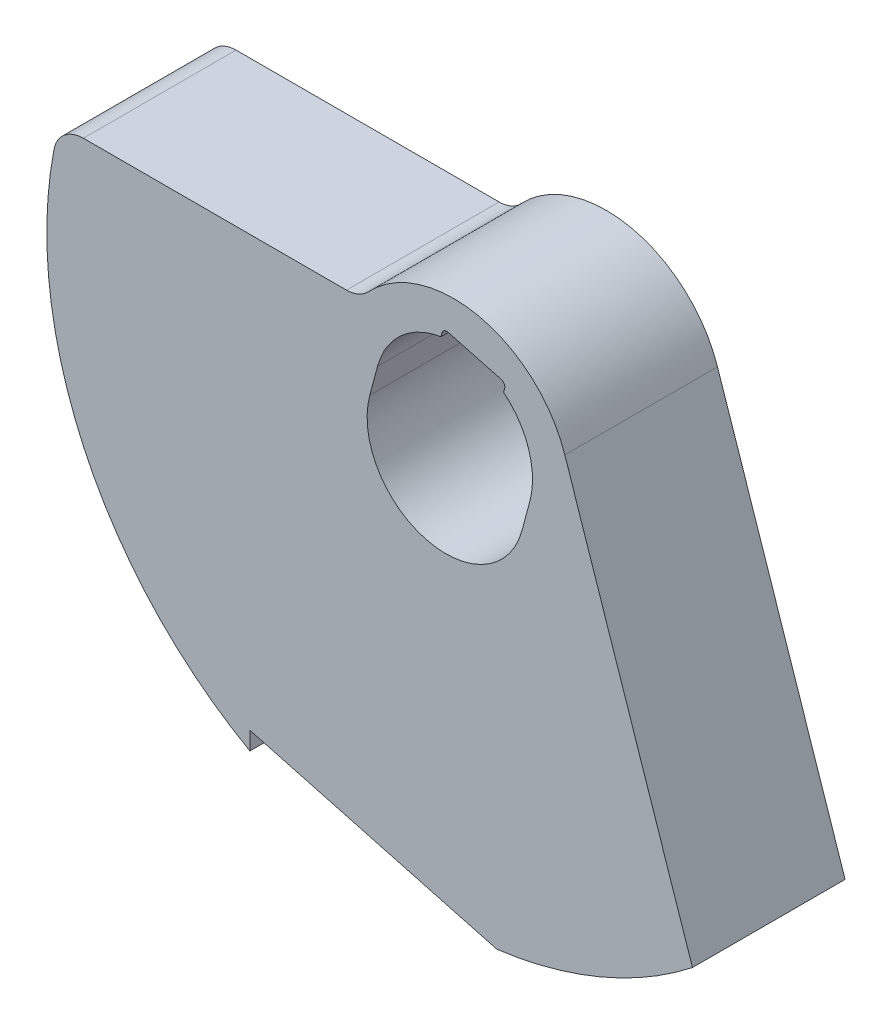
SolidWorks part; units mm, degrees
ref_plane "Front Plane" through (0, 0, 0) normal (0, 0, 1) x (1, 0, 0)
ref_plane "Top Plane" through (0, 0, 0) normal (0, 1, 0) x (1, 0, 0)
ref_plane "Right Plane" through (0, 0, 0) normal (1, 0, 0) x (0, 0, -1)
sketch "Sketch1" plane through (0, 0, 0) normal (0, 0, 1) x (1, 0, 0)
  line L0 (0, 40.7088) -> (0, -42.4788) construction
  line L1 (50.0011, 0) -> (-47.9361, 0) construction
  line L2 (0, 0) -> (4.815, 17.9697) construction
  line L3 (-7.4706, 2.0017) -> (6.4814, -1.7367) construction
  line L4 (-7.0762, 3.4738) -> (6.8758, -0.2646) construction
  line L5 (-3.8765, 1.0387) -> (-3.482, 2.5108)
  line L6 (4.2709, 0.4334) -> (3.8765, -1.0387)
  line L7 (-5.0653, 5.08) -> (-18.4566, 5.08)
  line L8 (6.0531, 3.3717) -> (7.0281, 0.4672)
  line L9 (12.9403, -3.6173) -> (17.147, -10.9034)
  line L10 (0, 0) -> (5.8427, -10.1199) construction
  line L11 (0, 0) -> (43.883, -11.7584) construction
  line L12 (12.7, 40.7088) -> (12.7, -42.4788) construction
  line L13 (50.0011, -9.398) -> (-47.9361, -9.398) construction
  line L14 (-1.0387, -3.8765) -> (-9.0244, -1.7367) construction
  line L15 (-9.9822, -16.7843) -> (-9.9822, -17.6991)
  line L16 (-9.9822, -16.7843) -> (2.5931, -20.1539)
  line L17 (2.8088, 5.0851) -> (0.11, 5.8082)
  line L18 (1.4594, 5.4467) -> (-6.5263, 7.5864) construction
  line L21 (2.9359, 4.578) -> (2.9884, 4.774)
  line L24 (-0.2536, 5.4326) -> (-0.2011, 5.6286)
  arc A0 (-3.8765, 1.0387) -> (3.8765, -1.0387) centre (0, 0) ccw
  arc A1 (6.1601, -0.0728) -> (6.1791, 0) centre (0.3944, 1.4721) ccw
  arc A2 (4.2709, 0.4334) -> (2.9359, 4.578) centre (0.3944, 1.4721) ccw
  arc A3 (7.0281, 0.4672) -> (12.6001, -3.4269) centre (12.446, 2.286) ccw
  arc A4 (6.0531, 3.3717) -> (-3.9548, 5.5602) centre (0.3944, 1.4721) ccw
  arc A5 (-19.953, 3.8443) -> (-9.9822, -17.6991) centre (0, 0) ccw
  arc A6 (12.6001, -3.4269) -> (12.9403, -3.6173) centre (12.6104, -3.8078) cw
  arc A7 (2.5931, -20.1539) -> (17.147, -10.9034) centre (0, 0) ccw
  arc A8 (-18.4566, 5.08) -> (-19.953, 3.8443) centre (-18.4566, 3.556) ccw
  arc A9 (-5.0653, 5.08) -> (-3.9548, 5.5602) centre (-5.0653, 6.604) ccw
  circle A10 centre (12.7, -9.398) radius 1.1938
  arc A11 (-0.2536, 5.4326) -> (-3.482, 2.5108) centre (0.3944, 1.4721) ccw
  arc A12 (2.8088, 5.0851) -> (2.9884, 4.774) centre (2.7431, 4.8397) cw
  arc A13 (-0.2011, 5.6286) -> (0.11, 5.8082) centre (0.0443, 5.5629) cw
  point P35 (-9.9822, 40.7088)
  point P36 (-9.9822, -42.4788)
  point P48 (1.5947, -0.4273)
  point P50 (6.4097, 17.5424)
  point P51 (-1.5947, 0.4273)
  point P52 (3.2202, 18.397)
  dimension "D1" = 8.0264
  dimension "D4" = 11.938
  dimension "D6" = 11.43
  dimension "D11" = 40.64
  dimension "D12" = 0.381
  dimension "D16" = 1.524
  dimension "D17" = 1.524
  dimension "D20" = 2.3876
  dimension "D24" = 0.254
  dimension "D2" = 15
  dimension "D5" = 5.08
  dimension "D7" = 2.286
  dimension "D8" = 12.446
  dimension "D9" = 60
  dimension "D10" = 9.398
  dimension "D13" = 15
  dimension "D14" = 18.796
  dimension "D15" = 9.9822
  dimension "D22" = 3.302
  dimension "D23" = 1.651
  dimension "D3" = 1.524
  dimension "D18" = 12.7
  dimension "D19" = 9.398
  dimension "D21" = 9.652
extrude "Boss-Extrude1" add sketch "Sketch1" against normal blind 7.7724 contours A9 L7 A8 A5 L15 L16 A7 L9 A6 A3 L8 A4 A10 A2 L6 A0 L5 region at (-3.0537, -7.1996, 0)
sketch "Sketch2" plane through (0, 0, 0) normal (0, 0, 1) x (1, 0, 0)
  line L0 (7.0281, 0.4672) -> (12.5499, -15.9813)
  arc A0 (2.5931, -20.1539) -> (17.147, -10.9034) centre (0, 0) ccw construction
  point P6 (0, 0)
  point P7 (0, 0)
extrude "Cut-Extrude1" cut sketch "Sketch2" against normal through all and the other way through all
